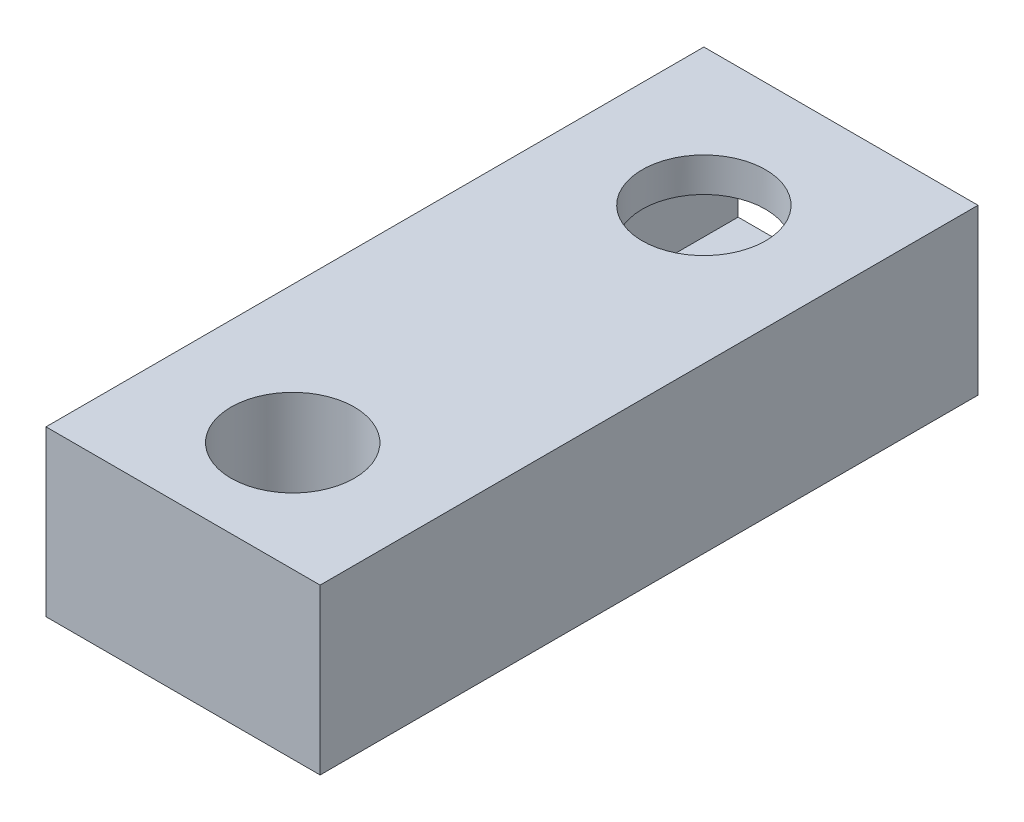
SolidWorks part; units mm, degrees
ref_plane "Alzado" through (0, 0, 0) normal (0, 0, 1) x (1, 0, 0)
ref_plane "Planta" through (0, 0, 0) normal (0, 1, 0) x (1, 0, 0)
ref_plane "Vista lateral" through (0, 0, 0) normal (1, 0, 0) x (0, 0, -1)
sketch "Croquis1" plane through (0, 0, 0) normal (0, 0, 1) x (1, 0, 0)
  line L1 (5, -3) -> (-5, -3)
  line L2 (5, -3) -> (5, 3)
  line L3 (5, 3) -> (-5, 3)
  line L4 (-5, -3) -> (-5, 3)
  line L5 (5, -3) -> (-5, 3) construction
  line L6 (5, 3) -> (-5, -3) construction
  point P0 (0, 0)
  dimension "D1" = 10
  dimension "D2" = 6
extrude "Saliente-Extruir1" add sketch "Croquis1" along normal blind 24
sketch "Croquis2" plane through (0, 0, 0) normal (0, 0, -1) x (-1, 0, 0)
  line L1 (3.75, -1.75) -> (-3.75, -1.75)
  line L2 (3.75, -1.75) -> (3.75, 1.75)
  line L3 (3.75, 1.75) -> (-3.75, 1.75)
  line L4 (-3.75, -1.75) -> (-3.75, 1.75)
  line L5 (3.75, -1.75) -> (-3.75, 1.75) construction
  line L6 (3.75, 1.75) -> (-3.75, -1.75) construction
  point P0 (0, 0)
  dimension "D1" = 7.5
  dimension "D2" = 3.5
extrude "Cortar-Extruir1" cut sketch "Croquis2" against normal blind 9
sketch "Croquis3" plane through (0, 3, 0) normal (0, 1, 0) x (1, 0, 0)
  line L1 (5, -12) -> (-4.3838, -12) construction
  line L2 (5, -24) -> (5, 0) construction
  line L3 (0, -24) -> (0, -20) construction
  line L4 (5, -24) -> (-5, -24) construction
  circle A1 centre (0, -20) radius 2.25
  dimension "D1" = 4
extrude "Cortar-Extruir2" cut sketch "Croquis3" against normal blind 9
sketch "Croquis4" plane through (0, -3, 0) normal (0, -1, 0) x (1, 0, 0)
  line L0 (0, 0) -> (0, 5)
  line L1 (-5, 0) -> (5, 0) construction
  circle A0 centre (0, 5) radius 2.25
  dimension "D1" = 5
extrude "Cortar-Extruir3" cut sketch "Croquis4" against normal blind 10 contours A0 region at (1.546, -3, 3.454)
